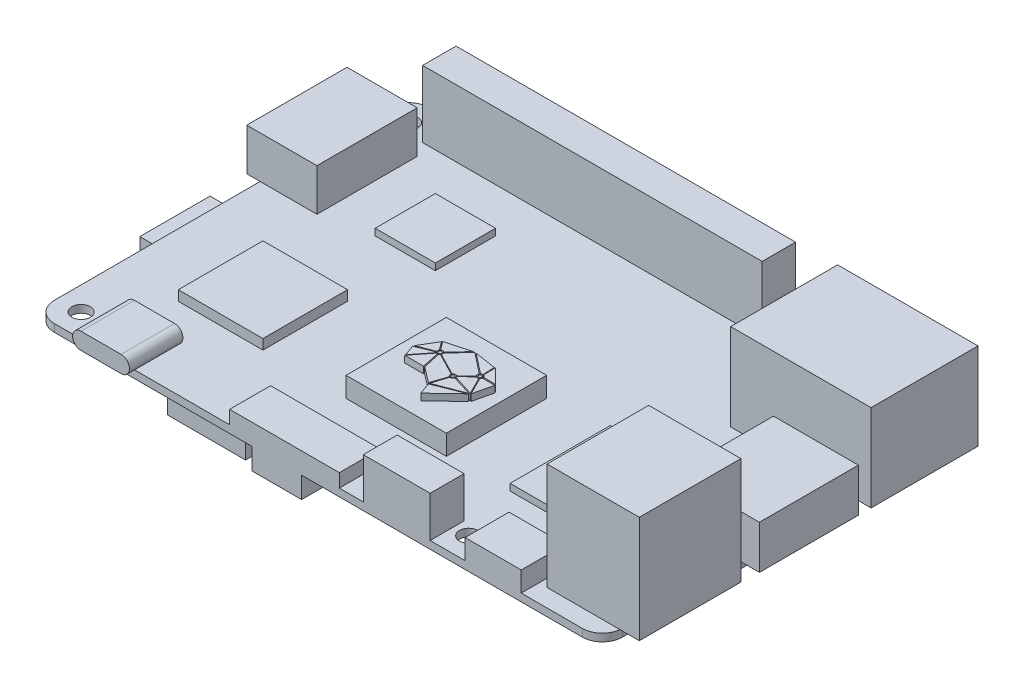
SolidWorks part; units mm, degrees
other "相机1"
other "相机2"
ref_plane "前视基准面" through (0, 0, 0) normal (0, 0, 1) x (1, 0, 0)
ref_plane "上视基准面" through (0, 0, 0) normal (0, 1, 0) x (1, 0, 0)
ref_plane "右视基准面" through (0, 0, 0) normal (1, 0, 0) x (0, 0, -1)
sketch "草图1" plane through (0, 0, 0) normal (0, 1, 0) x (1, 0, 0)
  line L1 (-42.5, -28) -> (42.5, -28)
  line L2 (-42.5, -28) -> (-42.5, 28)
  line L3 (-42.5, 28) -> (42.5, 28)
  line L4 (42.5, -28) -> (42.5, 28)
  line L5 (-42.5, -28) -> (42.5, 28) construction
  line L6 (-42.5, 28) -> (42.5, -28) construction
  point P0 (0, 0)
  dimension "D1" = 85
  dimension "D2" = 56
extrude "凸台-拉伸1" add sketch "草图1" along normal blind 1.14
fillet "圆角1" radius 3 4 edges at (-42.5, 0.57, -28) (-42.5, 0.57, 28) (42.5, 0.57, -28) (42.5, 0.57, 28)
sketch "草图2" plane through (0, 1.14, 0) normal (0, 1, 0) x (1, 0, 0)
  line L0 (-39.5, -28) -> (39.5, -28) construction
  line L1 (31.57, -10.14) -> (45.37, -10.14)
  line L2 (31.57, -10.14) -> (31.57, -25.34)
  line L3 (31.57, -25.34) -> (45.37, -25.34)
  line L4 (45.37, -10.14) -> (45.37, -25.34)
  line L5 (31.57, -10.14) -> (45.37, -25.34) construction
  line L6 (31.57, -25.34) -> (45.37, -10.14) construction
  line L7 (42.5, -25) -> (42.5, 25) construction
  point P0 (38.47, -17.74)
  dimension "D1" = 13.8
  dimension "D2" = 15.2
  dimension "D3" = 2.66
  dimension "D4" = 2.87
extrude "凸台-拉伸2" add sketch "草图2" along normal blind 16
sketch "草图3" plane through (0, 1.14, 0) normal (0, 1, 0) x (1, 0, 0)
  line L0 (-39.5, -28) -> (39.5, -28) construction
  line L1 (32.8041, 7.3) -> (45.5, 7.3)
  line L2 (32.8041, 7.3) -> (32.8041, -7.5)
  line L3 (32.8041, -7.5) -> (45.5, -7.5)
  line L4 (45.5, 7.3) -> (45.5, -7.5)
  line L5 (42.5, -10.14) -> (42.5, 25) construction
  dimension "D1" = 20.5
  dimension "D2" = 14.8
  dimension "D3" = 3
extrude "凸台-拉伸3" add sketch "草图3" along normal blind 6.5
sketch "草图5" plane through (0, 1.14, 0) normal (0, 1, 0) x (1, 0, 0)
  line L0 (39.5, 28) -> (-39.5, 28) construction
  line L1 (24.5, 25.2) -> (45.5, 25.2)
  line L2 (24.5, 25.2) -> (24.5, 9.2)
  line L3 (24.5, 9.2) -> (45.5, 9.2)
  line L4 (45.5, 25.2) -> (45.5, 9.2)
  line L5 (42.5, 7.3) -> (42.5, 25) construction
  dimension "D1" = 2.8
  dimension "D2" = 16
  dimension "D3" = 21
  dimension "D4" = 3
extrude "凸台-拉伸4" add sketch "草图5" along normal blind 13
sketch "草图6" plane through (0, 1.14, 0) normal (0, 1, 0) x (1, 0, 0)
  line L0 (-39, 24.5) -> (-38.9871, -24.5) construction
  line L1 (39.5, 28) -> (-39.5, 28) construction
  line L2 (-42.5, 25) -> (-42.5, -25) construction
  line L3 (19, 24.5) -> (19, -24.5004) construction
  circle A0 centre (-39, 24.5) radius 1.38
  circle A1 centre (19, 24.5) radius 1.38
  circle A2 centre (-38.9871, -24.5) radius 1.38
  circle A3 centre (19, -24.5) radius 1.38
  dimension "D1" = 2.76
  dimension "D2" = 49
  dimension "D3" = 3.5
  dimension "D4" = 3.5
  dimension "D5" = 58
  dimension "D6" = 49
  dimension "D7" = 3.5
extrude "切除-拉伸1" cut sketch "草图6" against normal through all
sketch "草图7" plane through (0, 1.14, 0) normal (0, 1, 0) x (1, 0, 0)
  line L0 (-42.5, 25) -> (-42.5, -25) construction
  line L1 (-35.39, 28) -> (15.41, 28)
  line L2 (-35.39, 28) -> (-35.39, 23)
  line L3 (-35.39, 23) -> (15.41, 23)
  line L4 (15.41, 28) -> (15.41, 23)
  line L5 (39.5, 28) -> (-39.5, 28) construction
  dimension "D1" = 7.11
  dimension "D2" = 50.8
  dimension "D3" = 5
  dimension "D4" = 0
extrude "凸台-拉伸5" add sketch "草图7" along normal blind 10
sketch "草图8" plane through (0, 1.14, 0) normal (0, 1, 0) x (1, 0, 0)
  line L0 (-35.39, 28) -> (-39.5, 28) construction
  line L1 (-34, 20.8) -> (-44.5, 20.8)
  line L2 (-34, 20.8) -> (-34, 5.8)
  line L3 (-34, 5.8) -> (-44.5, 5.8)
  line L4 (-44.5, 20.8) -> (-44.5, 5.8)
  line L5 (-42.5, 25) -> (-42.5, -25) construction
  dimension "D1" = 7.2
  dimension "D2" = 2
  dimension "D3" = 15
  dimension "D4" = 10.5
extrude "凸台-拉伸6" add sketch "草图8" along normal blind 6.3
sketch "草图9" plane through (0, 0, 0) normal (0, -1, 0) x (1, 0, 0)
  line L0 (-39.5, 28) -> (39.5, 28) construction
  line L1 (-42.5, -4.3) -> (-28, -4.3)
  line L2 (-42.5, -4.3) -> (-42.5, 10.2)
  line L3 (-42.5, 10.2) -> (-28, 10.2)
  line L4 (-28, -4.3) -> (-28, 10.2)
  line L5 (-42.5, -25) -> (-42.5, 25) construction
  dimension "D1" = 17.8
  dimension "D2" = 14.5
  dimension "D3" = 14.5
  dimension "D4" = 0
extrude "凸台-拉伸7" add sketch "草图9" along normal blind 2
sketch "草图10" plane through (0, -2, 0) normal (0, -1, 0) x (1, 0, 0)
  line L0 (-28, 10.2) -> (-42.5, 10.2) construction
  line L1 (-45.5, 9.2) -> (-36.6948, 9.2)
  line L2 (-45.5, 9.2) -> (-45.5, -1.3)
  line L3 (-45.5, -1.3) -> (-36.6948, -1.3)
  line L4 (-36.6948, 9.2) -> (-36.6948, -1.3)
  line L5 (-42.5, 10.2) -> (-42.5, -4.3) construction
  dimension "D1" = 1
  dimension "D2" = 3
  dimension "D3" = 10.5
extrude "凸台-拉伸8" add sketch "草图10" against normal up to surface (2 mm away) up to face at (-11.75, 0, 0.9833)
ref_plane "基准面1" through (0, 0, 29.5) normal (0, 0, 1) x (1, 0, 0)
sketch "草图11" plane through (0, 1.14, 0) normal (0, 1, 0) x (1, 0, 0)
  line L1 (-42.5, -5.7224) -> (-42.5, -40.0085) construction
sketch "草图12" plane through (0, 0, 29.5) normal (0, 0, 1) x (1, 0, 0)
  line L0 (-34, 2.39) -> (-28, 2.39) construction
  line L5 (-34, 3.64) -> (-28, 3.64)
  line L6 (-34, 1.14) -> (-28, 1.14)
  line L8 (-35.39, 1.14) -> (15.41, 1.14) construction
  arc A2 (-34, 3.64) -> (-34, 1.14) centre (-34, 2.39) ccw
  arc A3 (-28, 1.14) -> (-28, 3.64) centre (-28, 2.39) ccw
  point P2 (-31, 2.39)
  dimension "D1" = 6
  dimension "D2" = 2.5
  dimension "D3" = 0
  dimension "D4" = 8.5
extrude "凸台-拉伸9" add sketch "草图12" against normal blind 8
sketch "草图13" plane through (0, 1.14, 0) normal (0, 1, 0) x (1, 0, 0)
  line L0 (-42.5, 199994.2776) -> (-42.5, -200040.0085) construction
  line L1 (-13.26, -21.88) -> (3.15, -21.88)
  line L2 (-13.26, -21.88) -> (-13.26, -28)
  line L3 (-13.26, -28) -> (3.15, -28)
  line L4 (3.15, -21.88) -> (3.15, -28)
  line L5 (-28, -28) -> (39.5, -28) construction
  dimension "D1" = 29.24
  dimension "D2" = 16.41
  dimension "D3" = 6.12
  dimension "D4" = 0
extrude "凸台-拉伸10" add sketch "草图13" along normal blind 2
sketch "草图14" plane through (0, 1.14, 0) normal (0, 1, 0) x (1, 0, 0)
  line L0 (-42.5, 199994.2776) -> (-42.5, -200040.0085) construction
  line L1 (6.73, -22.92) -> (16.73, -22.92)
  line L2 (6.73, -22.92) -> (6.73, -28)
  line L3 (6.73, -28) -> (16.73, -28)
  line L4 (16.73, -22.92) -> (16.73, -28)
  line L5 (3.15, -28) -> (39.5, -28) construction
  dimension "D1" = 49.23
  dimension "D2" = 10
  dimension "D3" = 5.08
  dimension "D4" = 0
extrude "凸台-拉伸11" add sketch "草图14" along normal blind 6.12
sketch "草图15" plane through (0, 0, 0) normal (0, -1, 0) x (1, 0, 0)
  line L0 (-42.5, -199994.2776) -> (-42.5, 200040.0085) construction
  line L1 (-23.15, 27.43) -> (-11.45, 27.43)
  line L2 (-23.15, 27.43) -> (-23.15, 22.43)
  line L3 (-23.15, 22.43) -> (-11.45, 22.43)
  line L4 (-11.45, 27.43) -> (-11.45, 22.43)
  line L5 (-39.5, 28) -> (39.5, 28) construction
  dimension "D1" = 19.35
  dimension "D2" = 11.7
  dimension "D3" = 5
  dimension "D4" = 0.57
extrude "凸台-拉伸12" add sketch "草图15" along normal blind 2.81
sketch "草图16" plane through (0, 0, 0) normal (0, -1, 0) x (1, 0, 0)
  line L0 (-42.5, -199994.2776) -> (-42.5, 200040.0085) construction
  line L1 (-9.92, 28) -> (-2.5, 28)
  line L2 (-9.92, 28) -> (-9.92, 22.85)
  line L3 (-9.92, 22.85) -> (-2.5, 22.85)
  line L4 (-2.5, 28) -> (-2.5, 22.85)
  line L5 (-39.5, 28) -> (39.5, 28) construction
  dimension "D1" = 32.58
  dimension "D2" = 7.42
  dimension "D3" = 5.15
  dimension "D4" = 0
extrude "凸台-拉伸13" add sketch "草图16" along normal blind 3.18
sketch "草图17" plane through (0, 1.14, 0) normal (0, 1, 0) x (1, 0, 0)
  line L0 (-42.5, 199994.2776) -> (-42.5, -200040.0085) construction
  line L1 (21.96, -21.42) -> (30.36, -21.42)
  line L2 (21.96, -21.42) -> (21.96, -28)
  line L3 (21.96, -28) -> (30.36, -28)
  line L4 (30.36, -21.42) -> (30.36, -28)
  line L5 (16.73, -28) -> (39.5, -28) construction
  dimension "D1" = 64.46
  dimension "D2" = 8.4
  dimension "D3" = 6.58
  dimension "D4" = 0
extrude "凸台-拉伸14" add sketch "草图17" along normal blind 3
sketch "草图19" plane through (0, 1.14, 0) normal (0, 1, 0) x (1, 0, 0)
  line L0 (-42.5, 5.8) -> (-42.5, -25) construction
  line L1 (-33.1, -3.18) -> (-20.44, -3.18)
  line L2 (-33.1, -3.18) -> (-33.1, -15.84)
  line L3 (-33.1, -15.84) -> (-20.44, -15.84)
  line L4 (-20.44, -3.18) -> (-20.44, -15.84)
  line L5 (-28, -28) -> (-13.26, -28) construction
  dimension "D1" = 9.4
  dimension "D2" = 12.16
  dimension "D3" = 12.66
  dimension "D4" = 12.66
extrude "凸台-拉伸15" add sketch "草图19" along normal blind 1.5
sketch "草图20" plane through (0, 1.14, 0) normal (0, 1, 0) x (1, 0, 0)
  line L0 (-42.5, 5.8) -> (-42.5, -25) construction
  line L1 (-7.96, -0.88) -> (7.04, -0.88)
  line L2 (-7.96, -0.88) -> (-7.96, -15.88)
  line L3 (-7.96, -15.88) -> (7.04, -15.88)
  line L4 (7.04, -0.88) -> (7.04, -15.88)
  line L5 (3.15, -28) -> (6.73, -28) construction
  dimension "D1" = 34.54
  dimension "D2" = 12.12
  dimension "D3" = 15
  dimension "D4" = 15
extrude "凸台-拉伸16" add sketch "草图20" along normal blind 3
sketch "草图22" plane through (0, 1.14, 0) normal (0, 1, 0) x (1, 0, 0)
  line L0 (-42.5, 5.8) -> (-42.5, -25) construction
  line L1 (16.31, -0.61) -> (26.31, -0.61)
  line L2 (16.31, -0.61) -> (16.31, -15.61)
  line L3 (16.31, -15.61) -> (26.31, -15.61)
  line L4 (26.31, -0.61) -> (26.31, -15.61)
  line L5 (16.73, -28) -> (21.96, -28) construction
  dimension "D1" = 58.81
  dimension "D2" = 12.39
  dimension "D3" = 15
  dimension "D4" = 10
extrude "凸台-拉伸17" add sketch "草图22" along normal blind 1
sketch "草图23" plane through (0, 1.14, 0) normal (0, 1, 0) x (1, 0, 0)
  line L0 (-42.5, 5.8) -> (-42.5, -25) construction
  line L1 (-26.83, 16.35) -> (-17.83, 16.35)
  line L2 (-26.83, 16.35) -> (-26.83, 7.35)
  line L3 (-26.83, 7.35) -> (-17.83, 7.35)
  line L4 (-17.83, 16.35) -> (-17.83, 7.35)
  line L5 (-28, -28) -> (-13.26, -28) construction
  dimension "D1" = 15.67
  dimension "D2" = 35.35
  dimension "D3" = 9
  dimension "D4" = 9
extrude "凸台-拉伸18" add sketch "草图23" along normal blind 1
sketch "草图27" plane through (0, 4.14, 0) normal (0, 1, 0) x (1, 0, 0)
  line L0 (48.0142, 116.8123) -> (272.0142, 116.8123) construction
  line L1 (-3.2468, -6.6354) -> (-4.1852, -5.3743)
  line L2 (-4.1852, -5.3743) -> (-5.6693, -7.9008)
  line L3 (-5.6693, -7.9008) -> (-3.2934, -7.0174)
  line L4 (-3.2468, -7.1076) -> (-5.7594, -8.1226)
  line L5 (-5.7594, -8.1226) -> (-5.1711, -9.7646)
  line L6 (-5.1711, -9.7646) -> (-3.1595, -7.2008)
  line L7 (-3.0795, -7.2501) -> (-5.1639, -9.8992)
  line L8 (-5.1639, -9.8992) -> (-2.347, -9.8992)
  line L9 (-2.347, -9.8992) -> (-2.9011, -7.2901)
  line L10 (-2.7493, -7.2616) -> (-2.1748, -9.8992)
  line L11 (-2.1748, -9.8992) -> (0.1605, -11.667)
  line L12 (0.1605, -11.667) -> (0.9454, -9.3347)
  line L13 (0.7626, -8.8644) -> (-2.5789, -7.1387)
  line L14 (-2.5253, -7.0559) -> (0.8057, -8.7744)
  line L15 (1.0523, -9.3755) -> (0.3189, -11.667)
  line L16 (0.3189, -11.667) -> (4.596, -10.0331)
  line L17 (4.596, -10.0331) -> (1.5178, -9.1035)
  line L18 (4.596, -10.1262) -> (0.3189, -11.8428)
  line L19 (0.3189, -11.8428) -> (0.9454, -13.5937)
  line L20 (0.9454, -13.5937) -> (4.596, -10.1262)
  line L21 (1.5296, -8.9252) -> (4.645, -9.8992)
  line L22 (4.645, -9.8992) -> (3.3765, -7.3438)
  line L23 (2.9981, -7.3438) -> (1.4716, -8.7744)
  line L24 (1.3683, -8.6662) -> (2.8844, -7.2616)
  line L25 (3.4592, -7.2901) -> (4.7814, -9.8992)
  line L26 (4.7814, -9.8992) -> (5.4666, -7.0559)
  line L27 (5.4666, -7.0559) -> (3.6025, -7.0559)
  line L28 (3.6025, -6.8694) -> (5.3501, -6.8694)
  line L29 (5.3501, -6.8694) -> (3.2614, -4.7807)
  line L30 (3.2614, -4.7807) -> (3.2614, -6.5436)
  line L31 (3.1873, -6.5371) -> (3.1204, -4.7807)
  line L32 (3.1204, -4.7807) -> (-0.1003, -4.2874)
  line L33 (-0.1003, -4.2874) -> (2.9154, -6.6354)
  line L34 (2.8261, -6.7377) -> (-0.286, -4.2874)
  line L35 (-0.286, -4.2874) -> (-2.5295, -6.6787)
  line L36 (-2.6408, -6.5436) -> (-0.5024, -4.2874)
  line L37 (-0.5024, -4.2874) -> (-4.1034, -5.2786)
  line L38 (-4.1034, -5.2786) -> (-3.1533, -6.5373)
  circle A0 centre (-2.9011, -6.8715) radius 0.2414
  circle A1 centre (-2.9011, -6.8715) radius 0.4186
  circle A2 centre (3.1873, -6.9627) radius 0.2239
  circle A3 centre (3.1873, -6.9627) radius 0.4256
  circle A4 centre (1.1386, -8.9889) radius 0.2239
  circle A5 centre (1.1386, -8.9889) radius 0.3961
sketch "草图28" plane through (0, 1.14, 0) normal (0, 1, 0) x (1, 0, 0)
extrude "凸台-拉伸19" add sketch "草图27" along normal blind 1 contours A1 L7 L8 L9 | A1 L4 L5 L6 | A1 L1 L2 L3 | A5 L24 A3 L34 L35 A1 L14 | A5 L13 A1 L10 L11 L12 | A5 L15 L16 L17 | A5 L21 L22 A3 L23 | A3 L25 L26 L27 | A2 | A3 L31 L32 L33 | A3 L28 L29 L30 | A1 L36 L37 L38 | L19 L20 L18 | A0 | A4 region at (-4.3216, 4.14, 6.7293) region at (-2.4968, 4.14, 5.4321) region at (-4.6566, 4.14, 8.3071) region at (0.2127, 4.14, 6.7055) region at (-3.488, 4.14, 8.968) region at (2.0579, 4.14, 5.2879) region at (-0.8838, 4.14, 9.3378) region at (3.0922, 4.14, 8.6444) region at (3.9785, 4.14, 6.1521) region at (4.5418, 4.14, 8.0138) region at (2.0464, 4.14, 10.2564) region at (1.9534, 4.14, 11.8542) region at (3.1873, 4.14, 6.9627)
